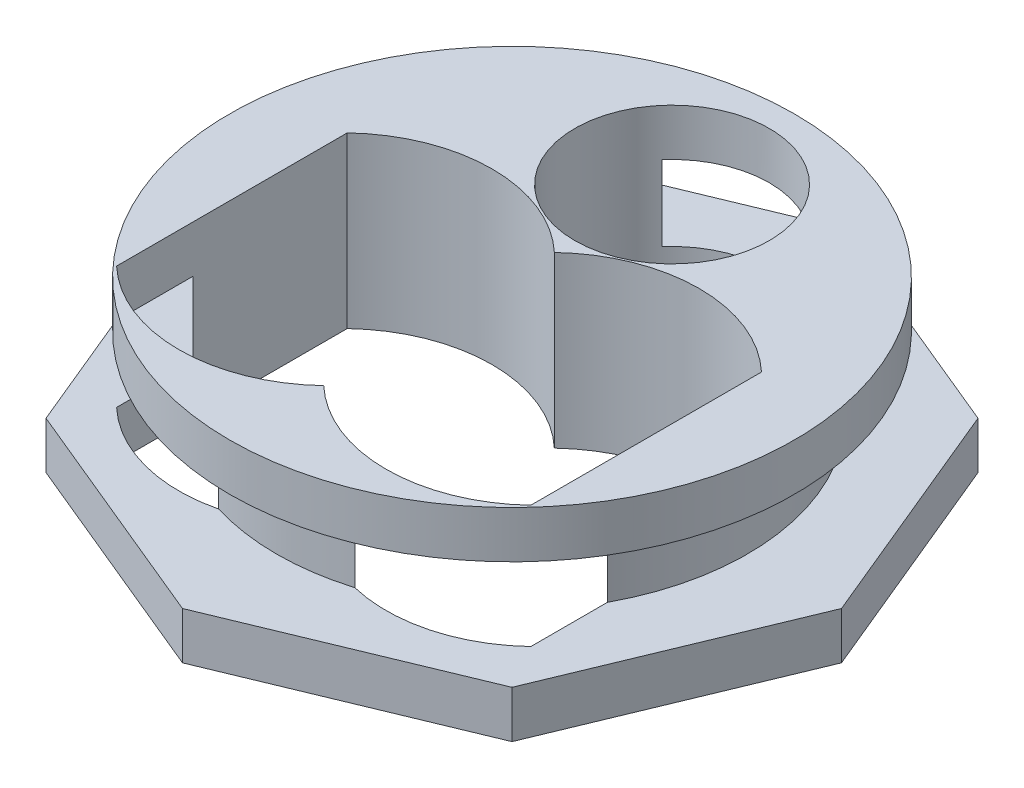
SolidWorks part; units mm, degrees
ref_plane "Front Plane" through (0, 0, 0) normal (0, 0, 1) x (1, 0, 0)
ref_plane "Top Plane" through (0, 0, 0) normal (0, 1, 0) x (1, 0, 0)
ref_plane "Right Plane" through (0, 0, 0) normal (1, 0, 0) x (0, 0, -1)
sketch "Sketch3" plane through (0, 0, 0) normal (0, 1, 0) x (1, 0, 0)
  line L1 (35, 0) -> (24.7487, 24.7487)
  line L2 (24.7487, 24.7487) -> (0, 35)
  line L3 (0, 35) -> (-24.7487, 24.7487)
  line L4 (-24.7487, 24.7487) -> (-35, 0)
  line L5 (-35, 0) -> (-24.7487, -24.7487)
  line L6 (-24.7487, -24.7487) -> (0, -35)
  line L7 (0, -35) -> (24.7487, -24.7487)
  line L8 (24.7487, -24.7487) -> (35, 0)
  circle A0 centre (0, 0) radius 32.3358 construction
  dimension "D1" = 35
extrude "Boss-Extrude1" add sketch "Sketch3" along normal blind 5
ref_axis "Axis2" through (0, 5, -35) along (0, 0, 1)
ref_axis "Axis3" through (0, 0, -35) along (0, 0, 1)
ref_plane "Plane1" through (0, 0, 0) normal (-1, 0, 0) x (0, 0, 1)
sketch "Sketch9" plane through (0, 5, 0) normal (0, 1, 0) x (1, 0, 0)
  line L0 (0, 38.0801) -> (0, -38.8207)
  line L1 (0, 2.75) -> (0, -2.75) construction
sketch "Sketch10" plane through (0, 5, 0) normal (0, 1, 0) x (1, 0, 0)
  line L1 (0, 38.0801) -> (47.253, 38.0801)
  line L2 (0, 38.0801) -> (0, -41.0679)
  line L3 (0, -41.0679) -> (47.253, -41.0679)
  line L4 (47.253, 38.0801) -> (47.253, -41.0679)
sketch "Sketch12" plane through (0, 5, 0) normal (0, 1, 0) x (1, 0, 0)
  circle A0 centre (0, 0) radius 25
extrude "Boss-Extrude2" add sketch "Sketch12" along normal blind 8 contours A0
sketch "Sketch17" plane through (0, 13, 0) normal (0, 1, 0) x (1, 0, 0)
  line L0 (0, 38.0801) -> (0, -38.8207) construction
  circle A0 centre (0, 17) radius 10.33
extrude "Cut-Extrude6" cut sketch "Sketch17" against normal blind 25 and the other way blind 9.8561 contours A0
sketch "Sketch23" plane through (0, 13, 0) normal (0, 1, 0) x (1, 0, 0)
  line L2 (-22.0422, 4.5) -> (-22.0422, -20)
  line L4 (-0.0422, 4.5) -> (-0.0422, -20)
  arc A0 (-22.0422, 4.5) -> (-0.0422, 4.5) centre (-11.0422, -7.119) cw
  arc A1 (-22.0422, -20) -> (-0.0422, -20) centre (-11.0422, -8.381) ccw
  point P6 (14.8691, -17.9405)
  dimension "D1" = 22
  dimension "D2" = 24.5
sketch "Sketch24" plane through (0, 13, 0) normal (0, 1, 0) x (1, 0, 0)
  line L2 (0, -30.0031) -> (33.426, -30.0031)
  line L3 (0, -30.0031) -> (0, 37.3911)
  line L4 (0, 37.3911) -> (33.426, 37.3911)
  line L5 (33.426, -30.0031) -> (33.426, 37.3911)
sketch "Sketch25" plane through (0, 13, 0) normal (0, 1, 0) x (1, 0, 0)
  circle A0 centre (0, 0) radius 30
extrude "Boss-Extrude3" add sketch "Sketch25" along normal blind 5
sketch "Sketch26" plane through (0, 18, 0) normal (0, 1, 0) x (1, 0, 0)
  line L0 (0, 38.0801) -> (0, -38.8207) construction
  circle A0 centre (0, 17) radius 10.33
extrude "Cut-Extrude9" cut sketch "Sketch26" against normal blind 5 contours A0
sketch "Sketch27" plane through (0, 18, 0) normal (0, 1, 0) x (1, 0, 0)
  line L0 (0, 38.0801) -> (0, -38.8207) construction
  line L2 (0, -20) -> (0, 4.5)
  line L4 (-22, -20) -> (-22, 4.5)
  arc A0 (-22, 4.5) -> (0, 4.5) centre (-11, -7.119) cw
  arc A1 (-22, -20) -> (0, -20) centre (-11, -8.381) ccw
extrude "Cut-Extrude10" cut sketch "Sketch27" against normal blind 45
mirror "Mirror8" about plane through (0, 0, 0) normal (-1, 0, 0) of "Cut-Extrude10"
